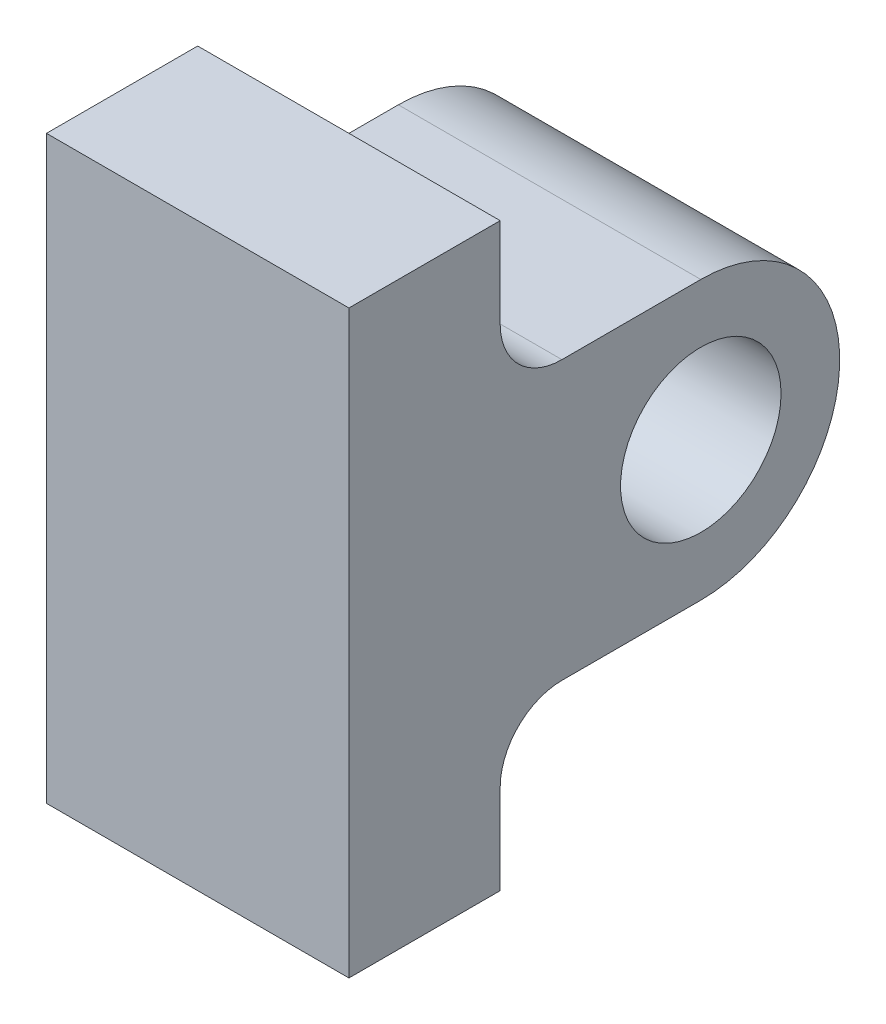
SolidWorks part; units mm, degrees
ref_plane "Front Plane" through (0, 0, 0) normal (0, 0, 1) x (1, 0, 0)
ref_plane "Top Plane" through (0, 0, 0) normal (0, 1, 0) x (1, 0, 0)
ref_plane "Right Plane" through (0, 0, 0) normal (1, 0, 0) x (0, 0, -1)
sketch "Sketch2" plane through (0, 0, 0) normal (1, 0, 0) x (0, 0, -1)
  line L0 (9, 4.5) -> (2.5, 4.5)
  line L1 (-2.5, 9.5) -> (2.5, 9.5)
  line L2 (-2.5, 9.5) -> (-2.5, -9.5)
  line L3 (-2.5, -9.5) -> (2.5, -9.5)
  line L4 (2.5, 9.5) -> (2.5, -9.5)
  line L5 (-2.5, 9.5) -> (2.5, -9.5) construction
  line L6 (-2.5, -9.5) -> (2.5, 9.5) construction
  line L7 (9, -4.5) -> (2.5, -4.5)
  line L8 (4.5, 0) -> (2.5, 0) construction
  circle A0 centre (9, 0) radius 4.5
  circle A1 centre (9, 0) radius 2.5
  point P0 (0, 0)
  point P12 (0, 0)
  point P13 (0, 0)
  dimension "D1" = 2
  dimension "D2" = 5
  dimension "D3" = 5
  dimension "D4" = 5
  dimension "D5" = 2
extrude "Boss-Extrude1" add sketch "Sketch2" along normal mid plane 10 contours L4 L1 L2 L3 | A0 L0 L4 L7 | A0 A1 region at (0, 0, -4.1529) region at (0, 3.092, -12.092) region at (0, 0, 0)
other "Move Face1" flip direction yes face at (5, 0, -11.5) face at (0, -9.5, 0) face at (0, 9.5, 0) face at (0, 0, 2.5) face at (-5, 0, -3.4375) face at (5, 0, -3.4375) offset 0.1 parameters "D1"=0.1
fillet "Fillet2" radius 2 2 edges at (0, -4.5, -2.5) (0, 4.5, -2.5)
